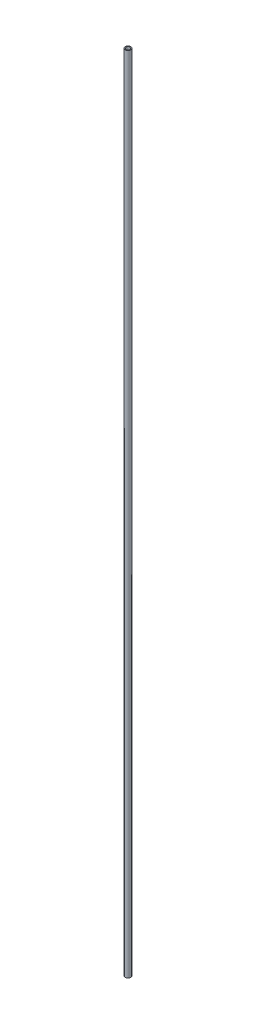
SolidWorks part; units mm, degrees
material "PVC Rigid"
ref_plane "Front Plane" through (0, 0, 0) normal (0, 0, 1) x (1, 0, 0)
ref_plane "Top Plane" through (0, 0, 0) normal (0, 1, 0) x (1, 0, 0)
ref_plane "Right Plane" through (0, 0, 0) normal (1, 0, 0) x (0, 0, -1)
sketch "Sketch1" plane through (0, 0, 0) normal (0, 1, 0) x (1, 0, 0)
  circle A0 centre (0, 0) radius 7.6454
  circle A1 centre (0, 0) radius 10.668
  dimension "D1" = 21.336
  dimension "D2" = 15.2908
extrude "Boss-Extrude1" add sketch "Sketch1" along normal blind 3048
